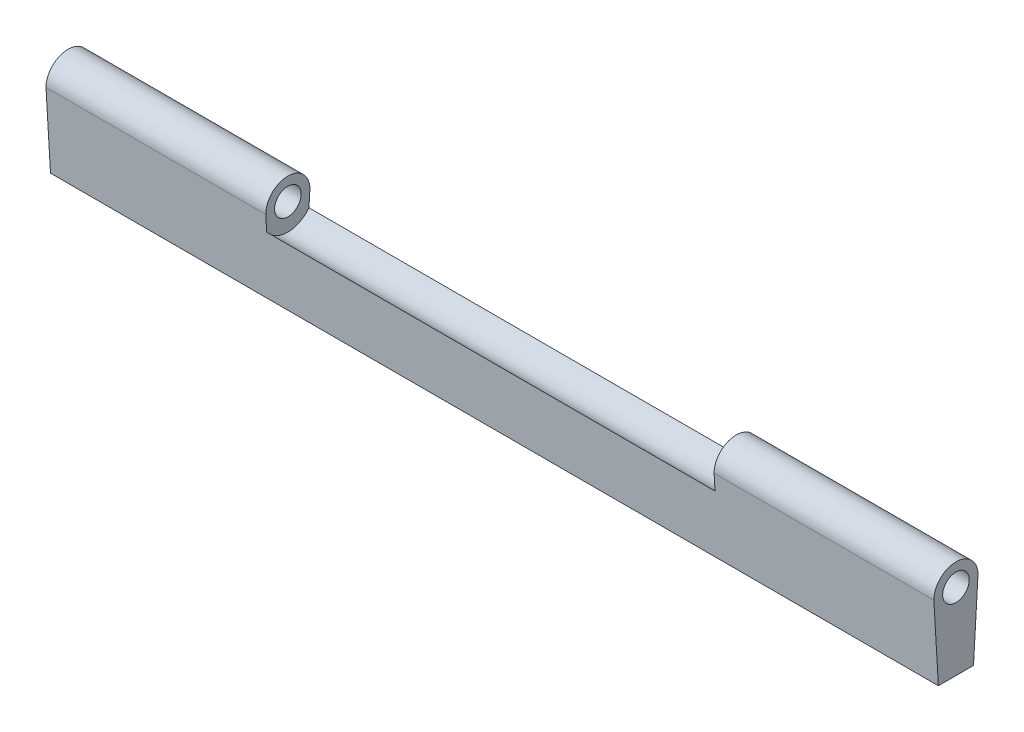
SolidWorks part; units mm, degrees
ref_plane "Front Plane" through (0, 0, 0) normal (0, 0, 1) x (1, 0, 0)
ref_plane "Top Plane" through (0, 0, 0) normal (0, 1, 0) x (1, 0, 0)
ref_plane "Right Plane" through (0, 0, 0) normal (1, 0, 0) x (0, 0, -1)
sketch "Sketch1" plane through (0, 0, 0) normal (1, 0, 0) x (0, 0, -1)
  line L0 (2, -8.7) -> (2.51, 0)
  line L5 (-2, -8.7) -> (2, -8.7)
  line L7 (-2.51, 0) -> (-2, -8.7)
  circle A0 centre (0, 0) radius 1.51
  arc A1 (2.51, 0) -> (-2.51, 0) centre (0, 0) ccw
  circle A3 centre (0, 0) radius 2.51 construction
  point P5 (0, -8.7)
  point P16 (2.51, 0)
  dimension "D1" = 3.02
  dimension "D3" = 8.7
  dimension "D4" = 4
  dimension "D2" = 1
extrude "Boss-Extrude1" add sketch "Sketch1" along normal blind 25
sketch "Sketch2" plane through (25, 0, 0) normal (1, 0, 0) x (0, 0, -1)
  line L0 (-2, -8.7) -> (2, -8.7)
  line L1 (2, -8.7) -> (2.4038, -1.8116)
  line L2 (2, -8.7) -> (2.51, 0) construction
  line L3 (-2.4038, -1.8116) -> (-2, -8.7)
  line L4 (-2.51, 0) -> (-2, -8.7) construction
  arc A0 (-1.51, 0) -> (1.51, 0) centre (0, 0) ccw construction
  circle A1 centre (0, 0) radius 1.51 construction
  arc A2 (-2.4038, -1.8116) -> (2.4038, -1.8116) centre (0, 0) ccw
  arc A4 (-3.01, 0) -> (3.01, 0) centre (0, 0) ccw construction
  dimension "D1" = 1.5
extrude "Boss-Extrude2" add sketch "Sketch2" along normal blind 51
sketch "Sketch3" plane through (76, 0, 0) normal (1, 0, 0) x (0, 0, -1)
  line L0 (-2.51, 0) -> (-2, -8.7)
  line L1 (-2, -8.7) -> (2, -8.7)
  line L2 (2, -8.7) -> (2.51, 0)
  circle A0 centre (0, 0) radius 1.51
  arc A1 (-2.51, 0) -> (2.51, 0) centre (0, 0) cw
  arc A2 (2.51, 0) -> (-2.51, 0) centre (0, 0) ccw construction
extrude "Boss-Extrude3" add sketch "Sketch3" along normal blind 25
sketch "Sketch4" plane through (0, 0, 0) normal (-1, 0, 0) x (0, 0, 1)
  line L0 (0, 0) -> (0, -8.7) construction
  line L1 (2, -8.7) -> (-2, -8.7) construction
